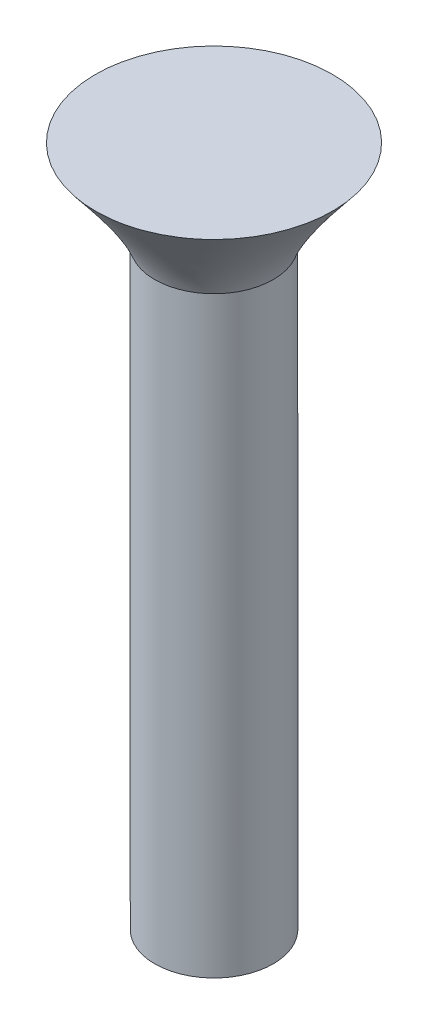
SolidWorks part; units mm, degrees
ref_plane "Front Plane" through (0, 0, 0) normal (0, 0, 1) x (1, 0, 0)
ref_plane "Top Plane" through (0, 0, 0) normal (0, 1, 0) x (1, 0, 0)
ref_plane "Right Plane" through (0, 0, 0) normal (1, 0, 0) x (0, 0, -1)
sketch "Sketch1" plane through (0, 0, 0) normal (0, 1, 0) x (1, 0, 0)
  circle A0 centre (0, 0) radius 2
  dimension "D1" = 4
extrude "Boss-Extrude1" add sketch "Sketch1" along normal blind 20
ref_plane "Plane1" through (0, 23, 0) normal (0, 1, 0) x (1, 0, 0)
sketch "Sketch2" plane through (0, 23, 0) normal (0, 1, 0) x (1, 0, 0)
  circle A0 centre (0, 0) radius 4
  dimension "D1" = 8
sketch "Sketch3" plane through (0, 20, 0) normal (0, 1, 0) x (1, 0, 0)
  circle A1 centre (0, 0) radius 2
  circle A2 centre (0, 0) radius 2
  dimension "D1" = 0
loft "Loft1" add profiles "Sketch3", "Sketch2" connector at (-1.8228, 20, -0.823) connector at (-1.8025, 23, -3.5708)
sketch "Sketch4" plane through (0, 0, 0) normal (0, 0, 1) x (1, 0, 0)
  line L0 (-4, 23) -> (-2, 20)
  line L1 (-2, 20) -> (-2, 23)
  line L2 (4, 23) -> (-4, 23) construction
